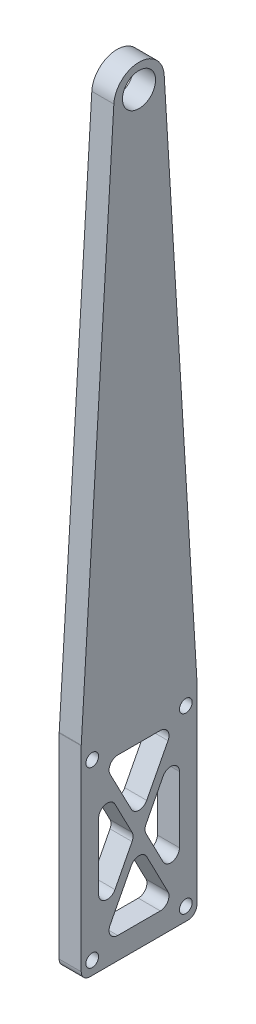
SolidWorks part; units mm, degrees
material "6061 Alloy"
ref_plane "Front Plane" through (0, 0, 0) normal (0, 0, 1) x (1, 0, 0)
ref_plane "Top Plane" through (0, 0, 0) normal (0, 1, 0) x (1, 0, 0)
ref_plane "Right Plane" through (0, 0, 0) normal (1, 0, 0) x (0, 0, -1)
sketch "Sketch1" plane through (0, 0, 0) normal (1, 0, 0) x (0, 0, -1)
  line L0 (-13.4747, 0) -> (13.4747, 0) construction
  line L1 (0, 0) -> (0, 160) construction
  line L2 (-13.4747, 0) -> (0, 160) construction
  line L3 (0, 160) -> (13.4747, 0) construction
  line L4 (13.4747, 0) -> (-13.4747, 0) construction
  line L8 (-13.4747, 0) -> (13.4747, 0) construction
  line L9 (-13.4747, 0) -> (-13.4747, -50) construction
  line L10 (13.4747, 0) -> (13.4747, -50) construction
  line L11 (-13.4747, -50) -> (13.4747, -50) construction
  line L16 (-16.645, -53.81) -> (16.645, -53.81)
  line L17 (-16.645, -53.81) -> (-16.645, 5.15)
  line L18 (16.645, -53.81) -> (16.645, 5.15)
  line L19 (-16.645, 5.15) -> (16.645, 5.15)
  line L20 (-16.645, 5.15) -> (-7.2492, 160.4386)
  line L21 (-7.2492, 160.4386) -> (7.2492, 160.4386) construction
  line L22 (7.2492, 160.4386) -> (16.645, 5.15)
  circle A0 centre (-13.4747, 0) radius 1.8288
  circle A1 centre (0, 160) radius 4.7625 construction
  circle A2 centre (13.4747, 0) radius 1.8288
  circle A3 centre (-13.4747, -50) radius 1.8288
  circle A4 centre (13.4747, -50) radius 1.8288
  arc A5 (-7.2492, 160.4386) -> (7.2492, 160.4386) centre (0, 160) cw
  point P4 (0, 0)
  point P7 (0, -53.81)
  dimension "D3" = 3.6576
  dimension "D4" = 9.525
  dimension "D9" = 2.5
  dimension "D1" = 26.9494
  dimension "D5" = 50
  dimension "D6" = 3.81
  dimension "D7" = 160
  dimension "D8" = 5.15
  dimension "D2" = 33.29
extrude "Boss-Extrude1" add sketch "Sketch1" along normal mid plane 6.35 contours A5 L20 L19 L22 | L19 L17 L16 L18 A4 A3 A2 A0 region at (0, -24.3153, 0) region at (0, 74.449, 0)
sketch "Sketch2" plane through (3.175, 0, 0) normal (1, 0, 0) x (0, 0, -1)
  line L3 (-11.645, -47.5) -> (-11.645, -2.5)
  line L4 (11.645, -47.5) -> (11.645, -2.5)
  line L5 (-11.645, -2.5) -> (11.645, -2.5)
  line L6 (-11.645, -47.5) -> (11.645, -47.5)
  line L7 (-11.645, -47.5) -> (11.645, -2.5) construction
  line L8 (-16.645, -53.81) -> (-16.645, 5.15) construction
  line L15 (11.645, -47.5) -> (-11.645, -2.5) construction
  line L24 (16.645, -53.81) -> (16.645, 5.15) construction
  line L31 (11.645, -44.7805) -> (-10.2375, -2.5)
  line L32 (-10.2375, -47.5) -> (11.645, -5.2195)
  line L33 (10.2375, -47.5) -> (-11.645, -5.2195)
  line L34 (-11.645, -44.7805) -> (10.2375, -2.5)
  line L35 (12.7551, -46.9254) -> (-10.5349, -1.9254) construction
  line L36 (10.5349, -48.0746) -> (-12.7551, -3.0746) construction
  line L37 (-10.5349, -48.0746) -> (12.7551, -3.0746) construction
  line L38 (-12.7551, -46.9254) -> (10.5349, -1.9254) construction
  circle A0 centre (13.4747, -50) radius 1.8288 construction
  circle A1 centre (13.4747, 0) radius 1.8288 construction
  point P0 (11.645, -25)
  point P2 (0, -47.5)
  point P28 (0, -25)
  dimension "D4" = 2.5
  dimension "D1" = 5
  dimension "D2" = 5
  dimension "D3" = 2.5
  dimension "D5" = 1.25
  dimension "D6" = 1.25
extrude "Cut-Extrude1" cut sketch "Sketch2" against normal through all contours L32 L31 L4 | L6 L33 L32 | L3 L34 L33 | L31 L34 L5 region at (3.175, -25, 8.2325) region at (3.175, -40.9065, 0) region at (3.175, -9.0935, 0) region at (3.175, -25, -8.2325)
fillet "Fillet1" radius 2.5 12 edges at (0, -2.5, -10.2375) (0, -22.2805, 0) (0, -2.5, 10.2375) (0, -5.2195, -11.645) (0, -44.7805, -11.645) (0, -25, -1.4075) (0, -47.5, 10.2375) (0, -47.5, -10.2375) (0, -27.7195, 0) (0, -25, 1.4075) (0, -5.2195, 11.645) (0, -44.7805, 11.645)
fillet "Fillet2" radius 2.5 4 edges at (0, 5.15, 16.645) (0, 5.15, -16.645) (0, -53.81, -16.645) (0, -53.81, 16.645)
hole_wizard "3/8 (0.3750) Dowel Hole1" positions "Sketch3" profile "Sketch4" hole size "3/8" standard "ANSI Inch" end condition through all
sketch "Sketch3" plane through (3.175, 0, 0) normal (1, 0, 0) x (0, 0, -1)
  line L0 (-7.2492, 160.4386) -> (7.2492, 160.4386) construction
  point P0 (0, 160.4386)
sketch "Sketch4" plane through (3.175, 160.4386, 0) normal (0, 1, 0) x (0, 0, -1)
  line L0 (0, 0) -> (0, 6.35)
  line L1 (0, 6.35) -> (4.7625, 6.35)
  line L2 (4.7625, 6.35) -> (4.7625, 0)
  line L5 (4.7625, 0) -> (0, 0)
  line L11 (0, -6.35) -> (0, 107.95) construction
  dimension "Thru Hole Dia." = 9.525
  dimension "Thru Hole Depth" = 6.35
